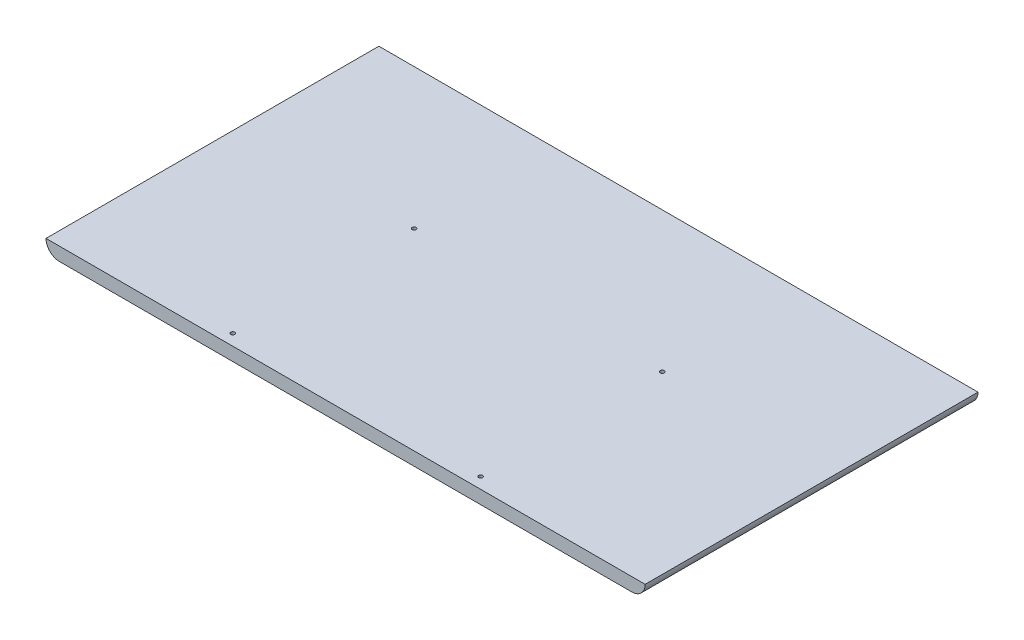
SolidWorks part; units mm, degrees
ref_plane "Front Plane" through (0, 0, 0) normal (0, 0, 1) x (1, 0, 0)
ref_plane "Top Plane" through (0, 0, 0) normal (0, 1, 0) x (1, 0, 0)
ref_plane "Right Plane" through (0, 0, 0) normal (1, 0, 0) x (0, 0, -1)
sketch "Sketch1" plane through (0, 0, 0) normal (0, 0, 1) x (1, 0, 0)
  line L11 (435.0394, -0.4715) -> (-14.9606, -0.4715)
  line L12 (435.0394, -0.4715) -> (435.0394, -10.4715)
  line L13 (435.0394, -10.4715) -> (-14.9606, -10.4715)
  line L14 (-14.9606, -0.4715) -> (-14.9606, -10.4715)
  dimension "D1" = 450
  dimension "D2" = 10
extrude "Boss-Extrude2" add sketch "Sketch1" along normal blind 250
sketch "Sketch2" plane through (0, 0, 0) normal (0, 0, -1) x (-1, 0, 0)
  line L3 (-435.0394, -0.4715) -> (14.9606, -0.4715) construction
  line L5 (-435.0394, -10.4715) -> (-435.0394, -0.4715) construction
  line L6 (14.9606, -0.4715) -> (14.9606, -10.4715) construction
  circle A0 centre (-25.0394, -5.4715) radius 3
  circle A1 centre (-210.0394, -5.4715) radius 3
  circle A3 centre (-395.0394, -5.4715) radius 3
  dimension "D1" = 5
  dimension "D2" = 5
  dimension "D3" = 5
  dimension "D4" = 40
  dimension "D5" = 40
  dimension "D6" = 185
extrude "Cut-Extrude1" cut sketch "Sketch2" against normal blind 20
fillet "Fillet1" radius 10 1 edges at (-14.9606, -10.4715, 125)
fillet "Fillet2" radius 10 1 edges at (435.0394, -10.4715, 125)
sketch "Sketch4" plane through (0, -0.4715, 0) normal (0, 1, 0) x (1, 0, 0)
  line L1 (-14.9606, -250) -> (-14.9606, 0) construction
  line L3 (435.0394, -250) -> (435.0394, 0) construction
  line L4 (-4.9606, -250) -> (425.0394, -250) construction
  circle A0 centre (303.1894, -241.66) radius 1.5
  circle A1 centre (116.8794, -241.66) radius 1.5
  circle A2 centre (116.8794, -105.35) radius 1.5
  circle A3 centre (303.1894, -105.35) radius 1.5
  dimension "D8" = 3
  dimension "D9" = 3
  dimension "D10" = 3
  dimension "D11" = 3
  dimension "D1" = 186.31
  dimension "D2" = 131.84
  dimension "D3" = 131.84
  dimension "D4" = 186.31
  dimension "D5" = 131.85
  dimension "D6" = 136.31
  dimension "D7" = 136.31
  dimension "D12" = 8.34
  dimension "D13" = 8.34
extrude "Cut-Extrude3" cut sketch "Sketch4" against normal blind 10
sketch "Sketch5" plane through (0, 0, 0) normal (0, 0, -1) x (-1, 0, 0)
  circle A2 centre (-395.0394, -5.4715) radius 3
  circle A3 centre (-210.0394, -5.4715) radius 3
  circle A4 centre (-25.0394, -5.4715) radius 3
extrude "Boss-Extrude3" add sketch "Sketch5" against normal blind 61
sketch "Sketch6" plane through (0, 0, 0) normal (0, 0, -1) x (-1, 0, 0)
  line L0 (4.9606, -10.4715) -> (-425.0394, -10.4715) construction
  line L1 (-435.0394, -0.4715) -> (14.9606, -0.4715) construction
  circle A0 centre (-395.3531, -5.4715) radius 1.5
  circle A1 centre (-210.0394, -5.4715) radius 1.5
  circle A2 centre (-25.0394, -5.4715) radius 1.5
  dimension "D1" = 40
  dimension "D2" = 40
  dimension "D3" = 185
  dimension "D4" = 5
  dimension "D5" = 5
  dimension "D6" = 5
extrude "Cut-Extrude4" cut sketch "Sketch6" against normal blind 20
